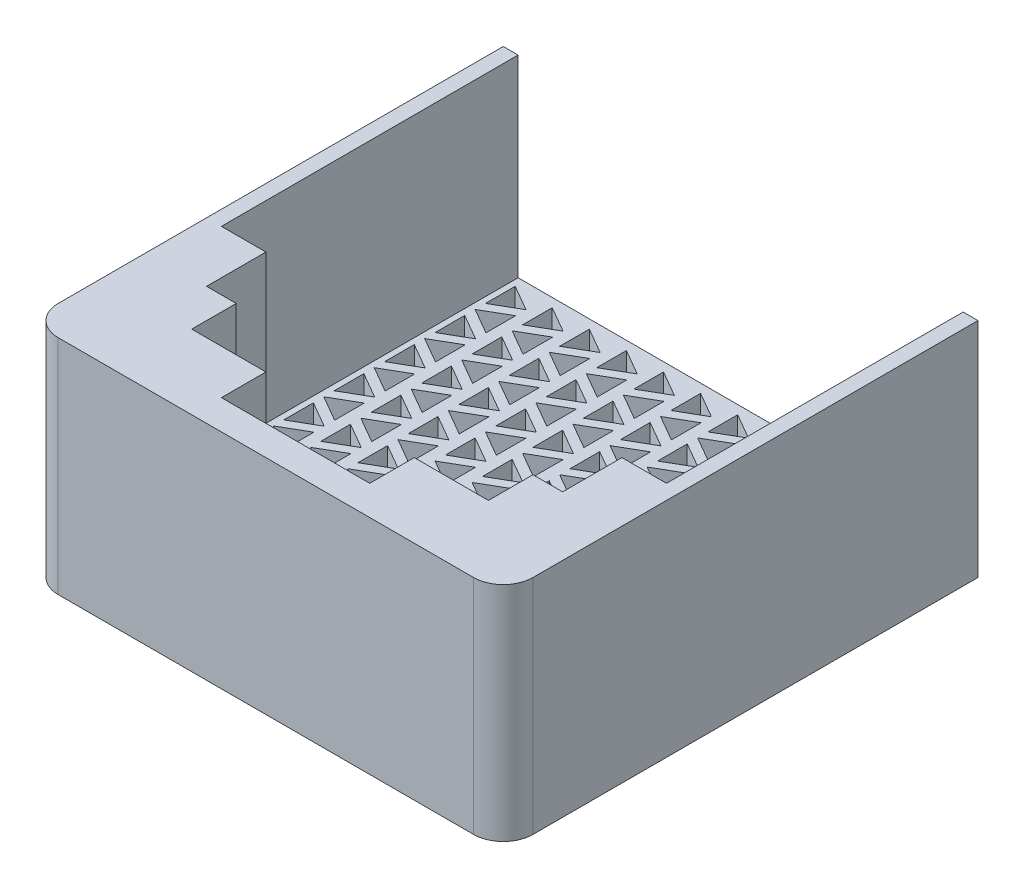
SolidWorks part; units mm, degrees
ref_plane "Front Plane" through (0, 0, 0) normal (0, 0, 1) x (1, 0, 0)
ref_plane "Top Plane" through (0, 0, 0) normal (0, 1, 0) x (1, 0, 0)
ref_plane "Right Plane" through (0, 0, 0) normal (1, 0, 0) x (0, 0, -1)
sketch "Sketch1" plane through (0, 0, 0) normal (0, 1, 0) x (1, 0, 0)
  line L1 (-80, 80) -> (80, 80)
  line L2 (-80, 80) -> (-80, -80)
  line L3 (-80, -80) -> (80, -80)
  line L4 (80, 80) -> (80, -80)
  line L5 (-80, 80) -> (80, -80) construction
  line L6 (-80, -80) -> (80, 80) construction
  point P0 (0, 0)
  dimension "D1" = 160
  dimension "D2" = 160
extrude "Boss-Extrude1" add sketch "Sketch1" along normal blind 75
sketch "Sketch2" plane through (0, 75, 0) normal (0, 1, 0) x (1, 0, 0)
  line L0 (-80, 80) -> (-80, -80) construction
  line L2 (-75, 80) -> (75, 80)
  line L4 (-75, 80) -> (-75, -70)
  line L5 (-75, -70) -> (75, -70)
  line L6 (75, 80) -> (75, -70)
  line L7 (80, -80) -> (80, 80) construction
  line L8 (80, 80) -> (-80, 80) construction
  line L9 (-80, -80) -> (80, -80) construction
  point P6 (0, 0)
  point P13 (0, 0)
  dimension "D1" = 5
  dimension "D2" = 5
  dimension "D3" = 0
  dimension "D4" = 10
extrude "Cut-Extrude1" cut sketch "Sketch2" against normal offset from surface (65 mm away) 10 up to face at (0, 0, 0)
sketch "Sketch3" plane through (0, 0, 70) normal (0, 0, -1) x (-1, 0, 0)
  line L0 (-75, 10) -> (75, 10) construction
  line L1 (-75, 75) -> (-60, 75)
  line L2 (-75, 75) -> (-75, 10)
  line L3 (-75, 10) -> (-60, 10)
  line L4 (-60, 75) -> (-60, 10)
  line L5 (0, 75) -> (0, 10) construction
  line L6 (75, 75) -> (-75, 75) construction
  line L7 (75, 10) -> (60, 10)
  line L8 (60, 75) -> (60, 10)
  line L9 (75, 75) -> (60, 75)
  line L10 (75, 75) -> (75, 10)
  dimension "D1" = 15
extrude "Boss-Extrude2" add sketch "Sketch3" along normal blind 50
sketch "Sketch4" plane through (0, 0, 70) normal (0, 0, -1) x (-1, 0, 0)
  line L0 (0, 75) -> (0, 10) construction
  line L1 (60, 75) -> (-60, 75) construction
  line L2 (75, 10) -> (-75, 10) construction
  line L3 (-60, 10) -> (60, 10) construction
  line L4 (-60, 75) -> (-50, 75)
  line L5 (-60, 75) -> (-60, 10)
  line L6 (-60, 10) -> (-50, 10)
  line L7 (-50, 75) -> (-50, 10)
  line L8 (60, 10) -> (50, 10)
  line L9 (50, 75) -> (50, 10)
  line L10 (60, 75) -> (50, 75)
  line L11 (60, 75) -> (60, 10)
  dimension "D1" = 10
extrude "Boss-Extrude3" add sketch "Sketch4" along normal blind 30
sketch "Sketch6" plane through (0, 10, 0) normal (0, 1, 0) x (1, 0, 0)
  line L0 (-73, -18) -> (-73, -8)
  line L1 (-73, -8) -> (-64.3397, -13)
  line L2 (-64.3397, -13) -> (-73, -18)
  line L3 (-75, -20) -> (-75, 80) construction
  line L4 (-75, -20) -> (-60, -20) construction
  dimension "D1" = 10
  dimension "D2" = 10
  dimension "D3" = 10
  dimension "D4" = 2
  dimension "D5" = 2
extrude "Cut-Extrude2" cut sketch "Sketch6" against normal through all and the other way through all
pattern_linear "LPattern1" count 6 spacing 17 along (0, 0, -1) count 12 spacing 12.5 along (1, 0, 0) of "Cut-Extrude2"
sketch "Sketch10" plane through (0, 10, 0) normal (0, 1, 0) x (1, 0, 0)
  line L0 (-64.3397, 0.5) -> (-73, -4.5)
  line L1 (-73, -4.5) -> (-64.3397, -9.5)
  line L2 (-64.3397, -9.5) -> (-64.3397, 0.5)
  line L4 (-64.3397, 4) -> (-64.3397, -13) construction
  line L5 (-73, -1) -> (-73, -8) construction
  point P2 (-64.3397, -4.5)
  point P4 (-64.3397, -4.5)
  point P13 (-73, -4.5)
  dimension "D1" = 10
  dimension "D2" = 10
  dimension "D3" = 10
  dimension "D4" = 0
  dimension "D5" = 0
extrude "Cut-Extrude3" cut sketch "Sketch10" against normal through all
pattern_linear "LPattern2" count 5 spacing 17 along (0, 0, -1) count 12 spacing 12.5 along (1, 0, 0) of "Cut-Extrude3"
fillet "Fillet1" radius 10 2 edges at (80, 37.5, 80) (-80, 37.5, 80)
sketch "Sketch11" plane through (0, 0, 70) normal (0, 0, -1) x (-1, 0, 0)
  line L0 (-50, 10) -> (50, 10) construction
  line L1 (-50, 75) -> (-25, 75)
  line L2 (-50, 75) -> (-50, 10)
  line L3 (-50, 10) -> (-25, 10)
  line L4 (-25, 75) -> (-25, 10)
  line L5 (0, 75) -> (0, 10) construction
  line L6 (50, 75) -> (-50, 75) construction
  line L7 (75, 10) -> (-75, 10) construction
  line L8 (50, 10) -> (25, 10)
  line L9 (25, 75) -> (25, 10)
  line L10 (50, 75) -> (25, 75)
  line L11 (50, 75) -> (50, 10)
  dimension "D1" = 25
extrude "Boss-Extrude4" add sketch "Sketch11" along normal blind 15
